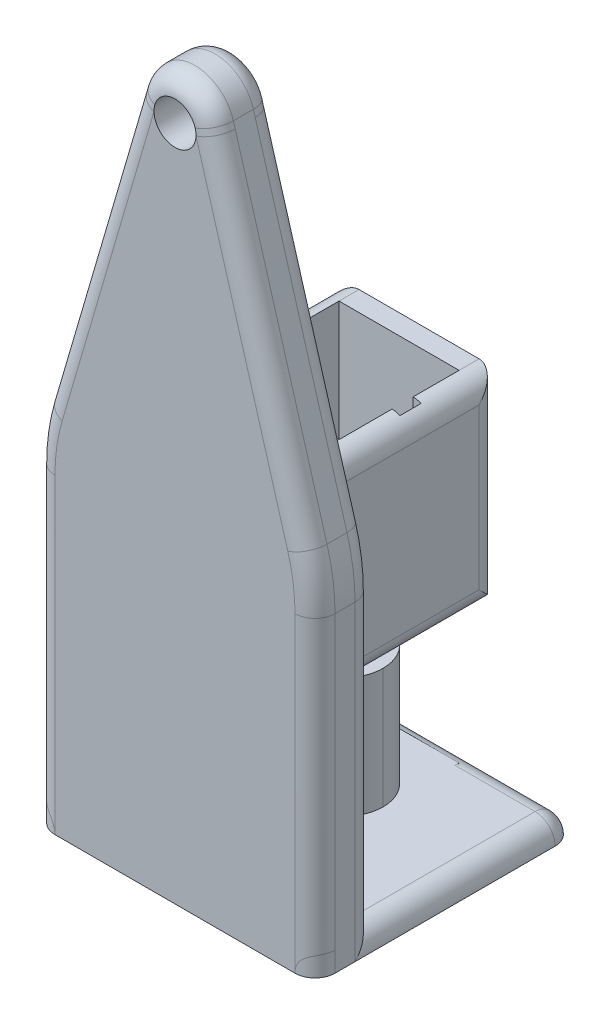
SolidWorks part; units mm, degrees
ref_plane "Front Plane" through (0, 0, 0) normal (0, 0, 1) x (1, 0, 0)
ref_plane "Top Plane" through (0, 0, 0) normal (0, 1, 0) x (1, 0, 0)
ref_plane "Right Plane" through (0, 0, 0) normal (1, 0, 0) x (0, 0, -1)
sketch "Sketch1" plane through (0, 0, 0) normal (0, 0, 1) x (1, 0, 0)
  line L0 (-40, 0) -> (40, 0)
  line L1 (40, 0) -> (40, 10)
  line L2 (40, 10) -> (-40, 10)
  line L3 (35, 10) -> (35, 90)
  line L4 (35, 90) -> (9.5975, 176.8085)
  line L5 (0, 0) -> (0, 184) construction
  line L6 (-35, 90) -> (-9.5975, 176.8085)
  line L7 (-35, 10) -> (-35, 90)
  line L8 (-40, 0) -> (-40, 10)
  circle A0 centre (0, 174) radius 10
  circle A1 centre (0, 174) radius 5.25
  point P4 (0, 174)
  point P12 (0, 10)
  dimension "D1" = 20
  dimension "D7" = 10.5
  dimension "D2" = 40
  dimension "D3" = 10
  dimension "D4" = 35
  dimension "D5" = 80
  dimension "D6" = 164
extrude "Boss-Extrude1" add sketch "Sketch1" along normal blind 15 contours L5 L0 L1 L2 | L2 L5 L6 L7 | L5 L2 L3 L4 | L0 L1 L2 L8 | A0 | A1 region at (20, 5, 0) region at (15.6489, 78.6458, 0) region at (-15.6489, 78.6458, 0)
sketch "Sketch2" plane through (0, 0, 0) normal (0, 0, -1) x (-1, 0, 0)
  line L1 (-35, 5) -> (35, 5)
  line L2 (-35, 5) -> (-35, 10)
  line L3 (-35, 10) -> (35, 10)
  line L4 (35, 5) -> (35, 10)
extrude "Boss-Extrude2" add sketch "Sketch2" along normal blind 50
sketch "Sketch3" plane through (0, 0, 0) normal (0, 0, -1) x (-1, 0, 0)
  line L0 (-10, 10) -> (10, 10)
  line L1 (35, 10) -> (40, 10) construction
  line L2 (10, 10) -> (10, 40)
  line L4 (10, 40) -> (-10, 40)
  line L5 (-10, 10) -> (-10, 40)
  line L6 (-15, 100) -> (-20, 100)
  line L7 (15, 50) -> (20, 50)
  line L8 (15, 50) -> (15, 100)
  line L9 (15, 100) -> (20, 100)
  line L10 (20, 50) -> (20, 100)
  line L11 (-15, 50) -> (-15, 100)
  line L12 (-15, 50) -> (-20, 50)
  line L13 (-20, 50) -> (-20, 100)
  dimension "D2" = 30
  dimension "D3" = 5
  dimension "D4" = 50
  dimension "D5" = 10
extrude "Boss-Extrude3" add sketch "Sketch3" along normal blind 46
fillet "Fillet1" radius 50 2 edges at (-35, 90, 7.5) (35, 90, 7.5)
fillet "Fillet3" radius 5 3 edges at (0, 10, -50) (-40, 10, 7.5) (40, 10, 7.5)
fillet "Fillet5" radius 5 14 edges at (35, 46.4173, 0) (34.4943, 89.9275, 0) (-35, 46.4173, 0) (-34.4943, 89.9275, 0) (-21.2926, 136.8428, 0) (0, 184, 0) (35, 46.4173, 15) (34.4943, 89.9275, 15) (-35, 46.4173, 15) (-34.4943, 89.9275, 15) (-21.2926, 136.8428, 15) (0, 184, 15) (21.2926, 136.8428, 0) (21.2926, 136.8428, 15)
fillet "Fillet7" radius 5 3 edges at (20, 75, -46) (20, 50, -23) (20, 100, -23)
fillet "Fillet8" radius 5 3 edges at (-20, 50, -23) (-20, 75, -46) (-20, 100, -23)
sketch "Sketch4" plane through (0, 40, 0) normal (0, 1, 0) x (1, 0, 0)
  line L0 (-40, 0) -> (40, 0) construction
  line L1 (-15, 0) -> (10, 0)
  line L2 (-15, 0) -> (-15, 17)
  line L3 (-15, 17) -> (10, 17)
  line L4 (10, 0) -> (10, 17)
  line L5 (-15, 46) -> (-15, 0) construction
  line L6 (10, 46) -> (10, 0) construction
  line L8 (10, 46) -> (-10, 46)
  line L9 (10, 46) -> (10, 37)
  line L10 (10, 37) -> (-10, 37)
  line L11 (-10, 46) -> (-10, 37)
  dimension "D1" = 17
  dimension "D2" = 20
extrude "Cut-Extrude1" cut sketch "Sketch4" against normal blind 30
fillet "Fillet11" radius 10 4 edges at (10, 25, -17) (-10, 25, -17) (-10, 25, -37) (10, 25, -37)
sketch "Sketch5" plane through (-15, 0, 0) normal (1, 0, 0) x (0, 0, -1)
  line L0 (46, 50) -> (0, 50) construction
  line L1 (46, 100) -> (41, 100)
  line L2 (46, 100) -> (46, 50)
  line L3 (46, 50) -> (41, 50)
  line L4 (41, 100) -> (41, 50)
  line L5 (46, 100) -> (0, 100) construction
  line L6 (11, 100) -> (6, 100)
  line L7 (11, 100) -> (11, 50)
  line L8 (11, 50) -> (6, 50)
  line L9 (6, 100) -> (6, 50)
  dimension "D1" = 5
  dimension "D2" = 30
  dimension "D3" = 5
extrude "Boss-Extrude4" add sketch "Sketch5" along normal blind 30
sketch "Sketch6" plane through (-20, 0, 0) normal (-1, 0, 0) x (0, 0, 1)
  line L0 (0, 50) -> (-17, 50) construction
  line L1 (-29.5, 54) -> (-24.25, 54)
  line L2 (-29.5, 54) -> (-29.5, 100)
  line L3 (-29.5, 100) -> (-24.25, 100)
  line L4 (-24.25, 54) -> (-24.25, 100)
  line L5 (0, 10) -> (0, 90) construction
  line L6 (-41, 100) -> (-11, 100) construction
  line L7 (-17, 50) -> (-17, 54) construction
  line L8 (-17, 50) -> (-37, 50) construction
  line L10 (-37, 50) -> (-37, 54) construction
  line L11 (-37, 54) -> (-29.5, 54) construction
  line L12 (-17, 54) -> (-24.25, 54) construction
  point P10 (0, 50)
  dimension "D1" = 4
  dimension "D2" = 7.25
  dimension "D3" = 5.25
  dimension "D4" = 17
  dimension "D5" = 20
extrude "Cut-Extrude2" cut sketch "Sketch6" against normal blind 32 and the other way blind 2 from surface contours L2 L3 L4 L1 starting at face at (-15, 75, -26)
sketch "Sketch7" plane through (0, 0, 0) normal (0, 0, -1) x (-1, 0, 0)
  line L0 (-35, 10) -> (-35, 5)
  line L1 (-35, 5) -> (35, 5)
  line L2 (35, 5) -> (35, 10)
  line L3 (35, 10) -> (40, 10)
  line L4 (40, 10) -> (40, 0)
  line L5 (40, 0) -> (-40, 0)
  line L6 (-40, 0) -> (-40, 10)
  line L7 (-40, 10) -> (-35, 10)
extrude "Cut-Extrude3" cut sketch "Sketch7" against normal blind 20
fillet "Fillet12" radius 5 6 edges at (-35, 7.5, 15) (35, 7.5, 15) (-35, 8.5355, -48.5355) (35, 8.5355, -48.5355) (-35, 10, -20) (35, 10, -20)
